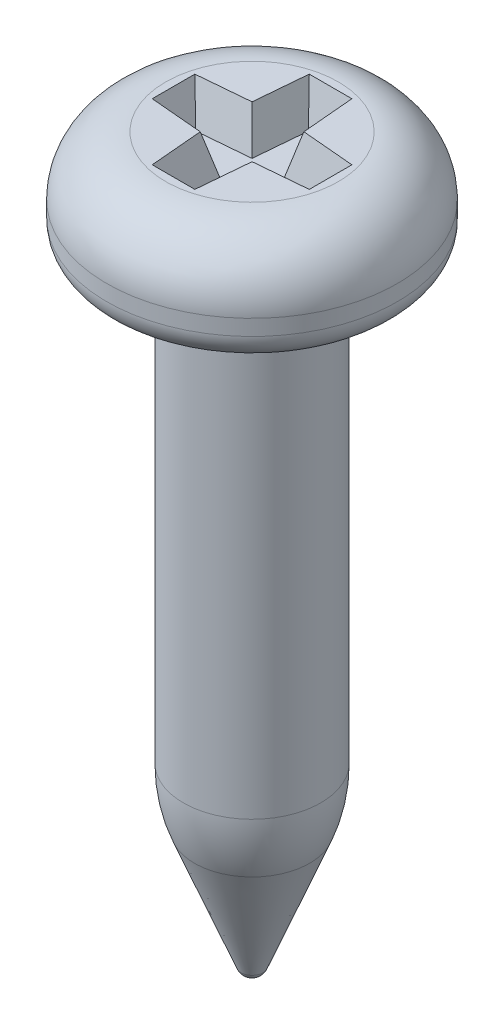
SolidWorks part; units mm, degrees
ref_plane "Front Plane" through (0, 0, 0) normal (0, 0, 1) x (1, 0, 0)
ref_plane "Top Plane" through (0, 0, 0) normal (0, 1, 0) x (1, 0, 0)
ref_plane "Right Plane" through (0, 0, 0) normal (1, 0, 0) x (0, 0, -1)
sketch "Sketch1" plane through (0, 0, 0) normal (0, 0, 1) x (1, 0, 0)
  line L0 (0, 0) -> (0, -9.3) construction
  line L2 (0.875, -6.9644) -> (0.875, -1.45)
  line L3 (1.025, -1.3) -> (1.5, -1.3)
  line L4 (1.85, -0.95) -> (1.85, -0.75)
  line L5 (1.1, 0) -> (0, 0)
  line L6 (0, 0) -> (0, -9.3)
  line L7 (0.7348, -7.7) -> (0.1395, -9.2052)
  arc A0 (1.85, -0.75) -> (1.1, 0) centre (1.1, -0.75) ccw
  arc A1 (1.5, -1.3) -> (1.85, -0.95) centre (1.5, -0.95) ccw
  arc A2 (0.875, -1.45) -> (1.025, -1.3) centre (1.025, -1.45) cw
  arc A3 (0.1395, -9.2052) -> (0, -9.3) centre (0, -9.15) cw
  arc A4 (0.7348, -7.7) -> (0.875, -6.9644) centre (-1.125, -6.9644) ccw
  point P13 (0.875, -1.3)
  dimension "D3" = 0.75
  dimension "D6" = 0.35
  dimension "D7" = 0.15
  dimension "D8" = 2
  dimension "D4" = 1.6
  dimension "D10" = 0.15
  dimension "D1" = 3.7
  dimension "D2" = 1.3
  dimension "D5" = 1.75
  dimension "D9" = 8
revolve "Revolve1" add sketch "Sketch1" angle 360 about L0
sketch "Sketch2" plane through (0, 0, 0) normal (0, 1, 0) x (1, 0, 0)
  line L0 (0, 1) -> (0, 0) construction
  line L1 (0, 0) -> (1, 0) construction
  line L2 (-0.2714, 1) -> (0.2714, 1)
  line L3 (0.2714, 1) -> (0.33, 0.33)
  line L4 (0.33, 0.33) -> (1, 0.2714)
  line L5 (1, 0.2714) -> (1, -0.2714)
  line L6 (-1, 0.2714) -> (-1, -0.2714)
  line L7 (-0.33, 0.33) -> (-1, 0.2714)
  line L8 (-0.2714, 1) -> (-0.33, 0.33)
  line L9 (-0.33, -0.33) -> (-1, -0.2714)
  line L10 (-0.2714, -1) -> (-0.33, -0.33)
  line L11 (-0.2714, -1) -> (0.2714, -1)
  line L12 (0.2714, -1) -> (0.33, -0.33)
  line L13 (0.33, -0.33) -> (1, -0.2714)
  point P18 (-1, 0)
  point P26 (0, 0)
  dimension "D1" = 95
  dimension "D2" = 2
  dimension "D3" = 0.66
extrude "Cut-Extrude1" cut sketch "Sketch2" against normal blind 0.5 draft 15
